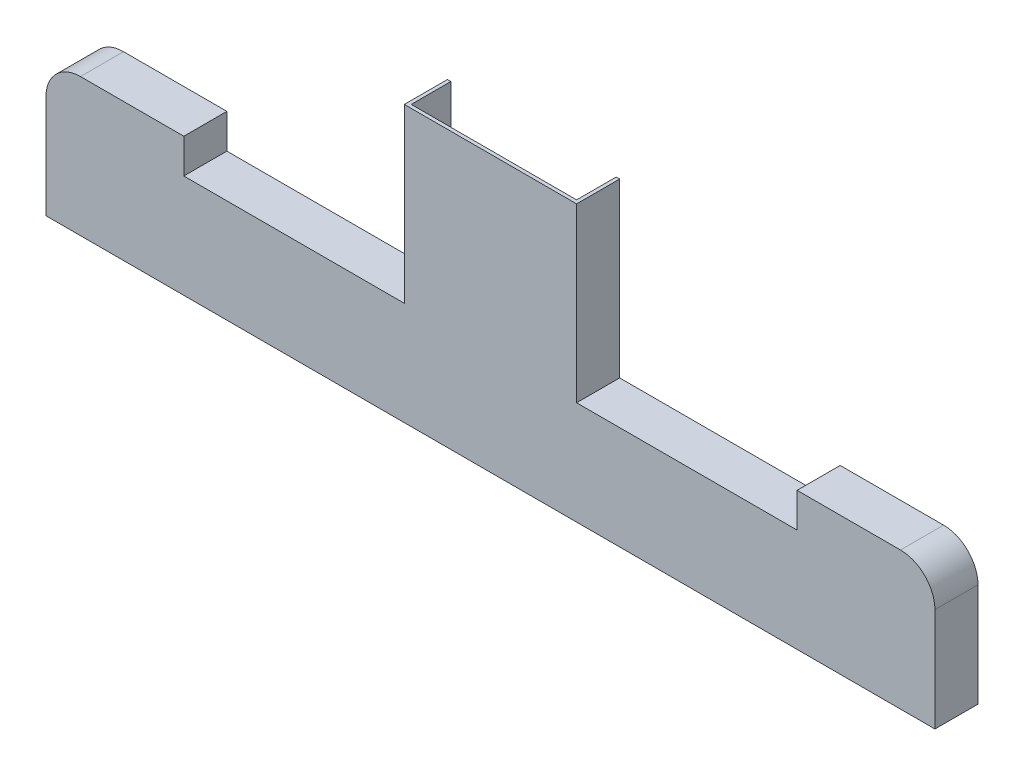
SolidWorks part; units mm, degrees
ref_plane "Front Plane" through (0, 0, 0) normal (0, 0, 1) x (1, 0, 0)
ref_plane "Top Plane" through (0, 0, 0) normal (0, 1, 0) x (1, 0, 0)
ref_plane "Right Plane" through (0, 0, 0) normal (1, 0, 0) x (0, 0, -1)
sketch "Sketch1" plane through (0, 0, 0) normal (0, 0, 1) x (1, 0, 0)
  line L0 (0, 0) -> (516, 0)
  line L1 (258, 0) -> (258, 22.3529) construction
  line L2 (258, 160) -> (258, -16.8627) construction
  line L3 (0, 0) -> (0, 60)
  line L4 (20, 80) -> (80, 80)
  line L5 (80, 80) -> (80, 60)
  line L6 (80, 60) -> (208, 60)
  line L7 (208, 60) -> (208, 160)
  line L8 (208, 160) -> (308, 160)
  line L9 (308, 60) -> (308, 160)
  line L10 (436, 80) -> (436, 60)
  line L11 (436, 60) -> (308, 60)
  line L12 (496, 80) -> (436, 80)
  line L13 (516, 0) -> (516, 60)
  arc A0 (0, 60) -> (20, 80) centre (20, 60) cw
  arc A1 (516, 60) -> (496, 80) centre (496, 60) ccw
  point P14 (208, 140.3088)
  point P15 (0, 0)
  dimension "D6" = 20
  dimension "D1" = 80
  dimension "D2" = 50
  dimension "D3" = 100
  dimension "D4" = 20
  dimension "D5" = 258
  dimension "D7" = 60
extrude "Boss-Extrude1" add sketch "Sketch1" against normal blind 25
sketch "Sketch2" plane through (0, 160, 0) normal (0, 1, 0) x (1, 0, 0)
  line L12 (308, 25) -> (208, 25) construction
  line L15 (210, 25) -> (306, 25)
  line L16 (210, 2) -> (306, 2)
  line L17 (306, 2) -> (306, 23)
  line L18 (306, 23) -> (210, 23)
  line L19 (210, 23) -> (210, 2)
  line L20 (210, 2) -> (306, 2)
  line L21 (306, 2) -> (306, 25)
  line L23 (210, 25) -> (210, 2)
  dimension "D2" = 2
extrude "Cut-Extrude1" cut sketch "Sketch2" against normal up to surface (100 mm away) up to face at (144, 60, -12.5)
shell "Shell3" thickness 2 removed face at (258, 80.4602, -25)
